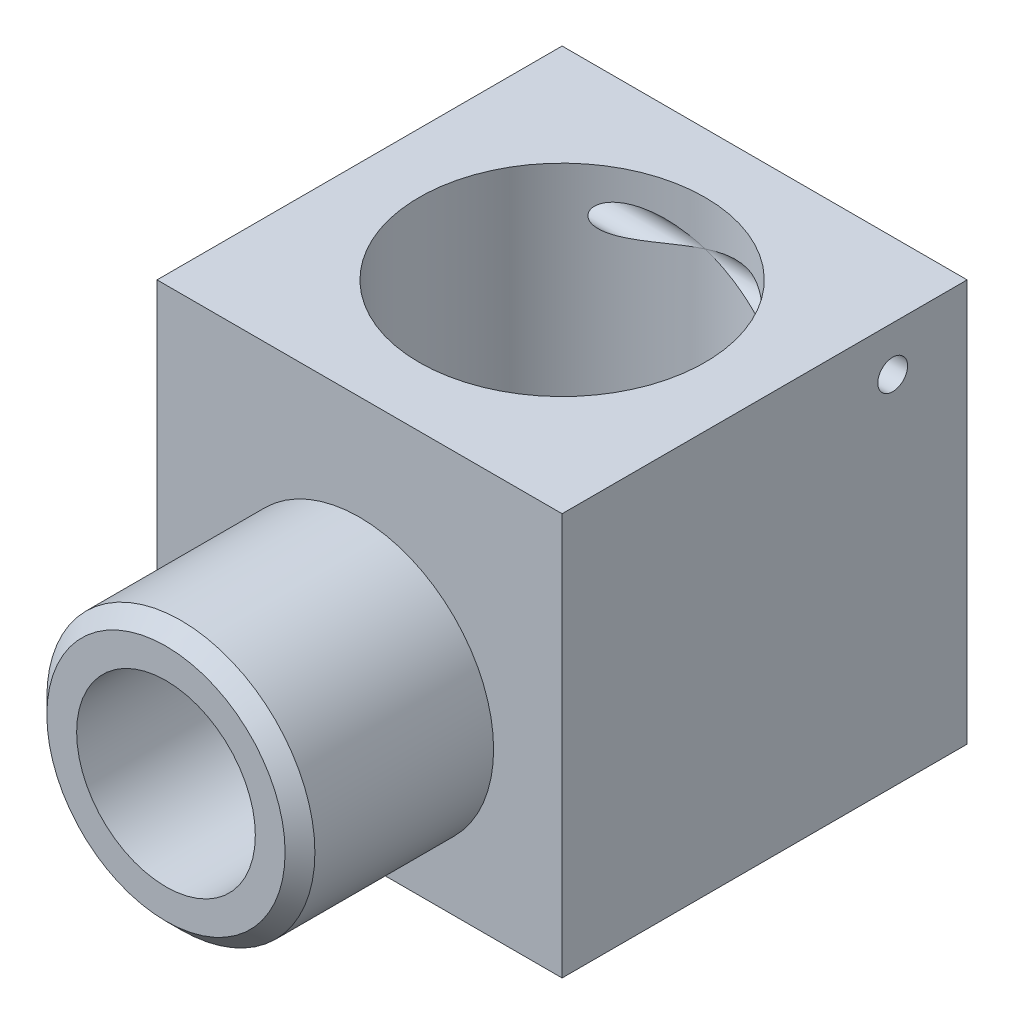
SolidWorks part; units mm, degrees
ref_plane "Front Plane" through (0, 0, 0) normal (0, 0, 1) x (1, 0, 0)
ref_plane "Top Plane" through (0, 0, 0) normal (0, 1, 0) x (1, 0, 0)
ref_plane "Right Plane" through (0, 0, 0) normal (1, 0, 0) x (0, 0, -1)
sketch "Sketch1" plane through (0, 0, 0) normal (0, 0, 1) x (1, 0, 0)
  circle A0 centre (0, 0) radius 12.8
extrude "Boss-Extrude1" add sketch "Sketch1" along normal blind 20.1
sketch "Sketch2" plane through (0, 0, 20.1) normal (0, 0, 1) x (1, 0, 0)
  circle A0 centre (0, 0) radius 4.5
extrude "Cut-Extrude1" cut sketch "Sketch2" against normal blind 6.5 flip side to cut
chamfer "Chamfer1" distance 0.5 angle 45 1 edges at (4.5, 0, 20.1)
sketch "Sketch3" plane through (0, 0, 20.1) normal (0, 0, 1) x (1, 0, 0)
  circle A0 centre (0, 0) radius 3
extrude "Cut-Extrude2" cut sketch "Sketch3" against normal blind 10
sketch "Sketch4" plane through (0, 0, 13.6) normal (0, 0, 1) x (1, 0, 0)
  line L1 (-6.8, -5.5) -> (6.8, -5.5)
  line L2 (-6.8, -5.5) -> (-6.8, 8)
  line L3 (-6.8, 8) -> (6.8, 8)
  line L4 (6.8, -5.5) -> (6.8, 8)
  circle A0 centre (0, 0) radius 12.8 construction
extrude "Cut-Extrude3" cut sketch "Sketch4" against normal up to surface (13.6 mm away) flip side to cut up to face at (12.8, 0, 0)
sketch "Sketch5" plane through (0, 8, 0) normal (0, 1, 0) x (1, 0, 0)
  circle A0 centre (0, -6.8) radius 4.8
extrude "Cut-Extrude4" cut sketch "Sketch5" against normal offset from surface (11.5 mm away) 2 up to face at (0, -5.5, 6.8)
sketch "Sketch7" plane through (6.8, 0, 0) normal (1, 0, 0) x (0, 0, -1)
  circle A0 centre (-2.5, 6.5) radius 0.5
extrude "Cut-Extrude6" cut sketch "Sketch7" against normal up to surface (13.6 mm away) up to face at (-6.8, 1.25, 6.8)
